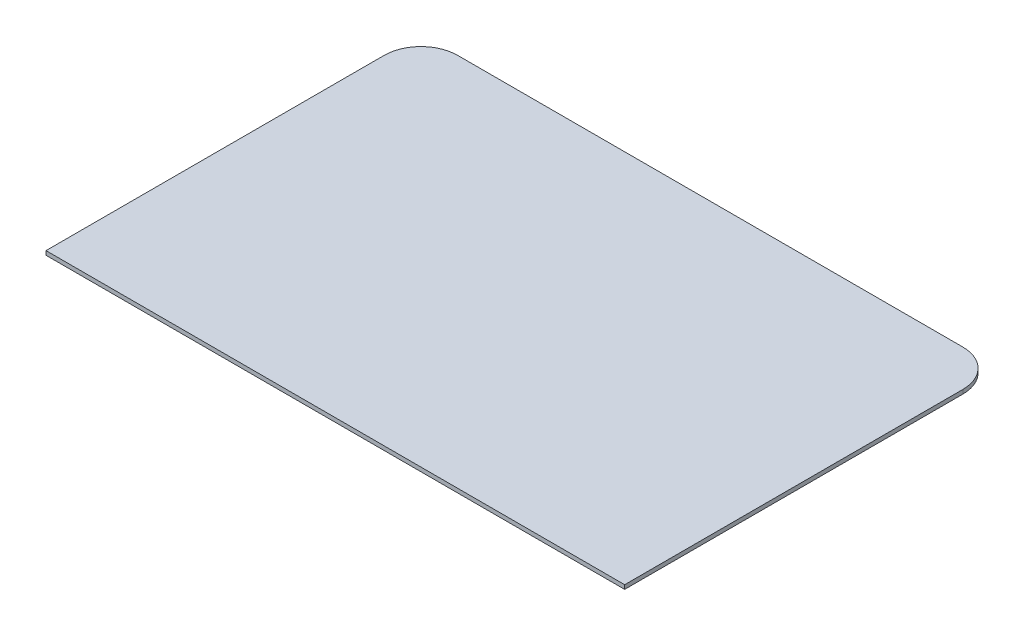
SolidWorks part; units mm, degrees
material "6061-T6 (SS)"
ref_plane "Front" through (0, 0, 0) normal (0, 0, 1) x (1, 0, 0)
ref_plane "Top" through (0, 0, 0) normal (0, 1, 0) x (1, 0, 0)
ref_plane "Right" through (0, 0, 0) normal (1, 0, 0) x (0, 0, -1)
sketch "Sketch1" plane through (0, 0, 0) normal (0, 1, 0) x (1, 0, 0)
  line L1 (225.425, -146.05) -> (-225.425, -146.05)
  line L2 (225.425, -146.05) -> (225.425, 146.05)
  line L3 (225.425, 146.05) -> (-225.425, 146.05)
  line L4 (-225.425, -146.05) -> (-225.425, 146.05)
  line L5 (225.425, -146.05) -> (-225.425, 146.05) construction
  line L6 (225.425, 146.05) -> (-225.425, -146.05) construction
  point P0 (0, 0)
  dimension "D1" = 450.85
  dimension "D2" = 292.1
extrude "Boss-Extrude1" add sketch "Sketch1" along normal blind 3.175
fillet "Fillet1" radius 28.575 2 edges at (-225.425, 1.5875, -146.05) (225.425, 1.5875, -146.05)
